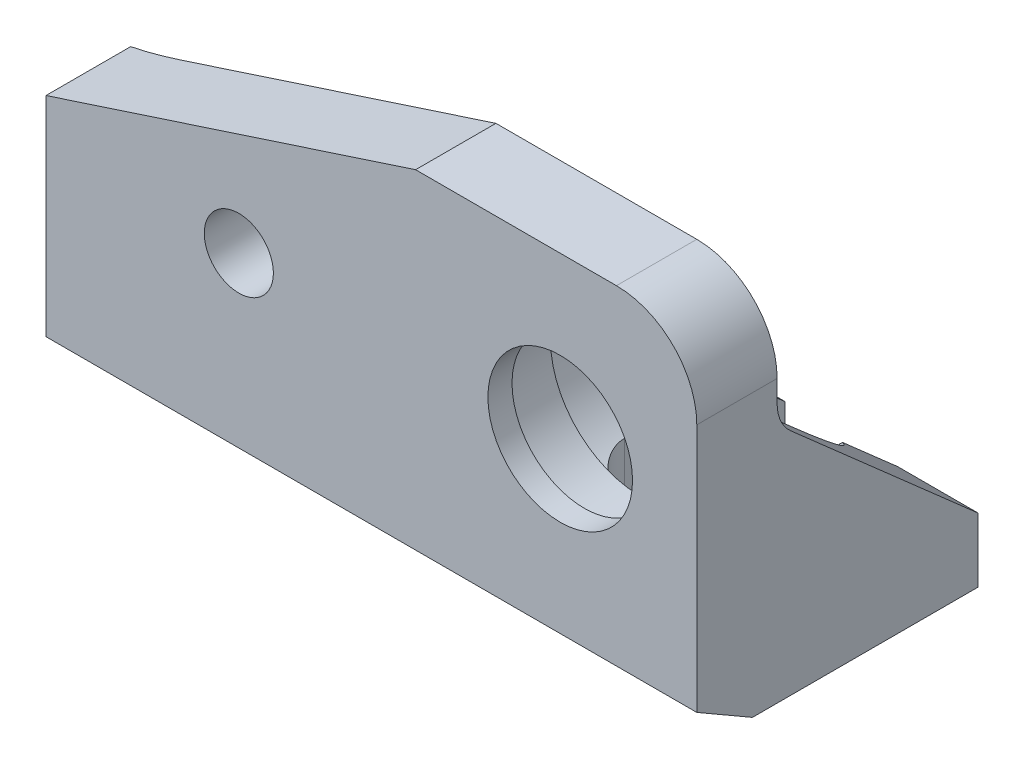
SolidWorks part; units mm, degrees
ref_plane "Front Plane" through (0, 0, 0) normal (0, 0, 1) x (1, 0, 0)
ref_plane "Top Plane" through (0, 0, 0) normal (0, 1, 0) x (1, 0, 0)
ref_plane "Right Plane" through (0, 0, 0) normal (1, 0, 0) x (0, 0, -1)
sketch "Sketch1" plane through (0, 0, 0) normal (0, 0, 1) x (1, 0, 0)
  line L0 (7, 20) -> (-18, 20)
  line L2 (-64, -25) -> (17, -25)
  line L3 (17, 10) -> (17, -25)
  line L4 (-18, 20) -> (-64, 5)
  line L5 (-64, 5) -> (-64, -25)
  circle A0 centre (0, 0) radius 9
  circle A1 centre (-40, 0) radius 4.3
  arc A2 (7, 20) -> (17, 10) centre (7, 10) cw
  dimension "D2" = 18
  dimension "D3" = 8.6
  dimension "D7" = 20
  dimension "D8" = 18
  dimension "D10" = 10
  dimension "D1" = 40
  dimension "D4" = 25
  dimension "D5" = 24
  dimension "D6" = 17
  dimension "D9" = 30
extrude "Boss-Extrude1" add sketch "Sketch1" along normal blind 10
sketch "Sketch3" plane through (-64, 0, 0) normal (-1, 0, 0) x (0, 0, 1)
  line L0 (0, -25) -> (-25, -25)
  line L1 (-25, -25) -> (-25, -17)
  line L2 (-25, -17) -> (0, 5)
  line L3 (0, 5) -> (0, -25)
  dimension "D1" = 25
  dimension "D2" = 8
extrude "Boss-Extrude2" add sketch "Sketch3" against normal blind 10
sketch "Sketch4" plane through (17, 0, 0) normal (1, 0, 0) x (0, 0, -1)
  line L4 (0, 5) -> (0, -25)
  line L5 (0, -25) -> (25, -25)
  line L6 (25, -25) -> (25, -17)
  line L7 (25, -17) -> (0, 5)
  line L8 (0, 5) -> (0, -25)
  line L9 (0, -25) -> (25, -25)
  line L10 (25, -25) -> (25, -17)
  line L11 (25, -17) -> (0, 5)
  dimension "D1" = 0
extrude "Boss-Extrude3" add sketch "Sketch4" against normal blind 10
sketch "Sketch5" plane through (0, 0, 0) normal (1, 0, 0) x (0, 0, -1)
  line L5 (25, -17) -> (0, 5)
  line L6 (25, -25) -> (25, -17)
  line L7 (0, -25) -> (25, -25)
  line L8 (0, -5.6569) -> (0, -25)
  line L9 (0, 5) -> (0, -5.6569)
  line L10 (25, -17) -> (0, 5)
  line L11 (25, -25) -> (25, -17)
  line L12 (0, -25) -> (25, -25)
  line L13 (0, -5.6569) -> (0, -25)
  line L14 (0, 5) -> (0, -5.6569)
  dimension "D1" = 0
extrude "Boss-Extrude4" add sketch "Sketch5" against normal blind 10 from offset 7 offset against normal yes
sketch "Sketch2" plane through (0, 0, 0) normal (0, 0, -1) x (-1, 0, 0)
  circle A0 centre (0, 0) radius 11.2
  dimension "D1" = 22.4
extrude "Cut-Extrude1" cut sketch "Sketch2" against normal blind 7 and the other way through all
sketch "Sketch6" plane through (17, 0, 0) normal (1, 0, 0) x (0, 0, -1)
  line L0 (-10, -25) -> (-10, -21)
  line L1 (-10, -25) -> (-10, 10) construction
  line L2 (-10, -21) -> (-3.0718, -25)
  line L3 (-10, -25) -> (25, -25) construction
  line L4 (-3.0718, -25) -> (-10, -25)
  dimension "D1" = 30
  dimension "D2" = 4
extrude "Cut-Extrude2" cut sketch "Sketch6" against normal through all
fillet "Fillet1" radius 5 7 edges at (-59, 5, 0) (13.511, 5, 0) (7, -16.8715, 0) (-17, -10, 0) (-13.511, 5, 0) (-7, -16.8715, 0)
sketch "Sketch7" plane through (0, -25, 0) normal (0, -1, 0) x (1, 0, 0)
  line L0 (-59, -25) -> (-59, 14.5657) construction
  line L1 (-54, -25) -> (-64, -25) construction
  line L2 (-12, -25) -> (-12, 15.4608) construction
  line L3 (-17, -25) -> (-7, -25) construction
  line L4 (12, -25) -> (12, 15.4608) construction
  line L5 (7, -25) -> (17, -25) construction
  circle A0 centre (-59, -20) radius 2.6
  circle A1 centre (-59, -1) radius 2.6
  circle A2 centre (-12, -1) radius 2.6
  circle A3 centre (-12, -20) radius 2.6
  circle A4 centre (12, -20) radius 2.6
  circle A5 centre (12, -1) radius 2.6
  dimension "D3" = 5.2
  dimension "D1" = 5
  dimension "D2" = 19
extrude "Cut-Extrude3" cut sketch "Sketch7" against normal blind 8
sketch "Sketch8" plane through (0, 0, -25) normal (0, 0, -1) x (-1, 0, 0)
  circle A0 centre (0, 0) radius 13
  dimension "D1" = 26
extrude "Cut-Extrude4" cut sketch "Sketch8" against normal up to surface (25 mm away) up to face at (-35.7, 0, 0)
chamfer "Chamfer1" distance 0.6 angle 45 6 edges at (12, -25, -22.6) (12, -25, -3.6) (-12, -25, -3.6) (-12, -25, -22.6) (-59, -25, -22.6) (-59, -25, -3.6)
